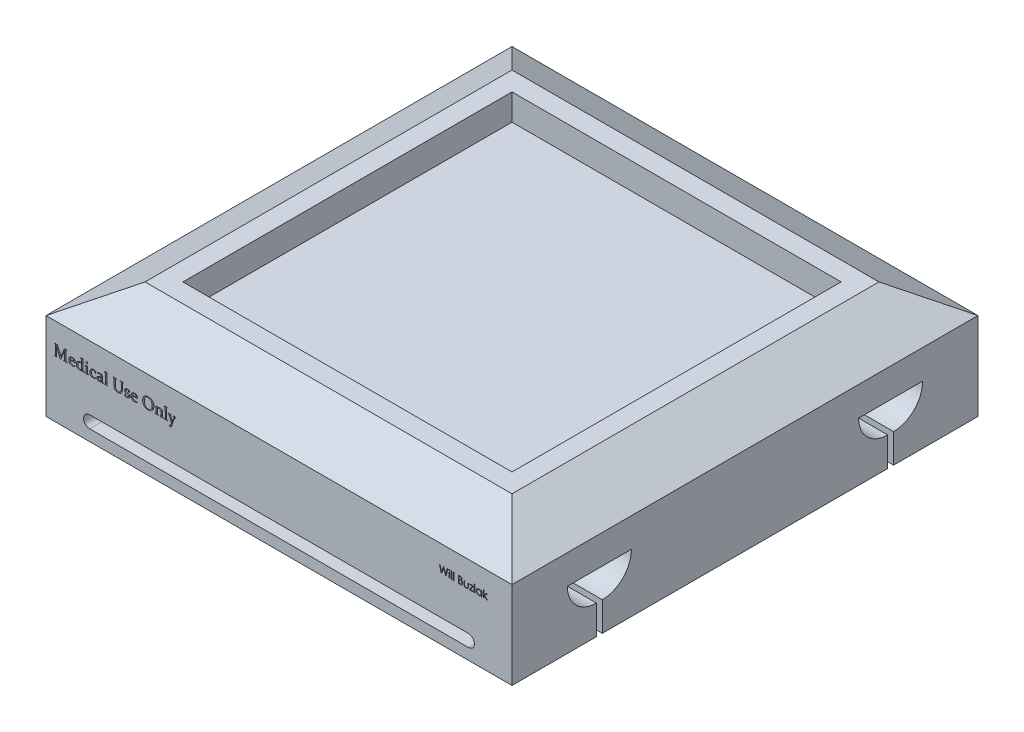
SolidWorks part; units mm, degrees
ref_plane "Front Plane" through (0, 0, 0) normal (0, 0, 1) x (1, 0, 0)
ref_plane "Top Plane" through (0, 0, 0) normal (0, 1, 0) x (1, 0, 0)
ref_plane "Right Plane" through (0, 0, 0) normal (1, 0, 0) x (0, 0, -1)
sketch "Sketch1" plane through (0, 0, 0) normal (0, 1, 0) x (1, 0, 0)
  line L1 (-101.6, -101.6) -> (101.6, -101.6)
  line L2 (-101.6, -101.6) -> (-101.6, 101.6)
  line L3 (-101.6, 101.6) -> (101.6, 101.6)
  line L4 (101.6, -101.6) -> (101.6, 101.6)
  line L5 (-101.6, -101.6) -> (101.6, 101.6) construction
  line L6 (-101.6, 101.6) -> (101.6, -101.6) construction
  point P0 (0, 0)
  dimension "D1" = 203.2
  dimension "D2" = 203.2
ref_plane "Plane1" through (0, 12.7, 0) normal (0, 1, 0) x (1, 0, 0)
sketch "Sketch2" plane through (0, 12.7, 0) normal (0, 1, 0) x (1, 0, 0)
  line L1 (-80.01, -80.01) -> (80.01, -80.01)
  line L2 (-80.01, -80.01) -> (-80.01, 80.01)
  line L3 (-80.01, 80.01) -> (80.01, 80.01)
  line L4 (80.01, -80.01) -> (80.01, 80.01)
  line L5 (-80.01, -80.01) -> (80.01, 80.01) construction
  line L6 (-80.01, 80.01) -> (80.01, -80.01) construction
  point P0 (0, 0)
  dimension "D1" = 160.02
  dimension "D2" = 160.02
loft "Loft2" add profiles "Sketch1", "Sketch2"
sketch "Sketch3" plane through (0, 12.7, 0) normal (0, 1, 0) x (1, 0, 0)
  line L1 (-71.755, -71.755) -> (71.755, -71.755)
  line L2 (-71.755, -71.755) -> (-71.755, 71.755)
  line L3 (-71.755, 71.755) -> (71.755, 71.755)
  line L4 (71.755, -71.755) -> (71.755, 71.755)
  line L5 (-71.755, -71.755) -> (71.755, 71.755) construction
  line L6 (-71.755, 71.755) -> (71.755, -71.755) construction
  point P0 (0, 0)
  dimension "D1" = 143.51
  dimension "D2" = 143.51
extrude "Cut-Extrude1" cut sketch "Sketch3" against normal blind 11.43
extrude "Boss-Extrude1" add sketch "Sketch1<3>" against normal blind 38.1
sketch "Sketch1<3>" plane through (0, 0, 0) normal (0, 1, 0) x (1, 0, 0) same geometry as "Sketch1"
sketch "Sketch7" plane through (-101.6, 0, 0) normal (-1, 0, 0) x (0, 0, 1)
  line L1 (-64.77, -25.4) -> (-64.77, -38.1)
  line L2 (-101.6, -38.1) -> (101.6, -38.1) construction
  line L4 (-64.77, -38.1) -> (-62.23, -38.1)
  line L5 (-77.47, -12.7) -> (-49.53, -12.7)
  line L7 (-62.23, -25.4) -> (-62.23, -38.1)
  line L8 (0, 0) -> (0, -38.1) construction
  arc A3 (-64.77, -25.4) -> (-77.47, -12.7) centre (-64.77, -12.7) cw
  arc A4 (-49.53, -12.7) -> (-62.23, -25.4) centre (-62.23, -12.7) cw
  dimension "D2" = 2.54
  dimension "D3" = 12.7
  dimension "D4" = 12.7
  dimension "D1" = 62.23
sketch "Sketch8" plane through (0, 0, 101.6) normal (0, 0, 1) x (1, 0, 0)
  text T0 "Medical Use Only" font "Constantia" height in points 18
  text T1 "Will Buziak"
extrude "Cut-Extrude3" cut sketch "Sketch8" against normal blind 2.54
extrude "Cut-Extrude4" cut sketch "Sketch7" against normal through all
mirror "Mirror1" about plane through (0, 0, 0) normal (0, 0, 1) of "Cut-Extrude4"
sketch "Sketch9" plane through (0, 0, -101.6) normal (0, 0, -1) x (-1, 0, 0)
  line L0 (0, 0) -> (0, -38.1) construction
  line L1 (-101.6, -38.1) -> (101.6, -38.1) construction
  line L2 (-101.6, -19.05) -> (101.6, -19.05) construction
  line L3 (-101.6, -38.1) -> (-101.6, 0) construction
  line L4 (101.6, -38.1) -> (101.6, 0) construction
  line L5 (-82.55, -30.5943) -> (82.55, -30.5943) construction
  line L6 (-82.55, -27.94) -> (82.55, -27.94)
  line L7 (-82.55, -33.2486) -> (82.55, -33.2486)
  arc A1 (-82.55, -27.94) -> (-82.55, -33.2486) centre (-82.55, -30.5943) ccw
  arc A2 (82.55, -33.2486) -> (82.55, -27.94) centre (82.55, -30.5943) ccw
  point P13 (0, -30.5943)
  dimension "D1" = 2.6543
  dimension "D2" = 8.89
  dimension "D3" = 19.05
  dimension "D4" = 19.05
extrude "Cut-Extrude6" cut sketch "Sketch9" against normal through all
